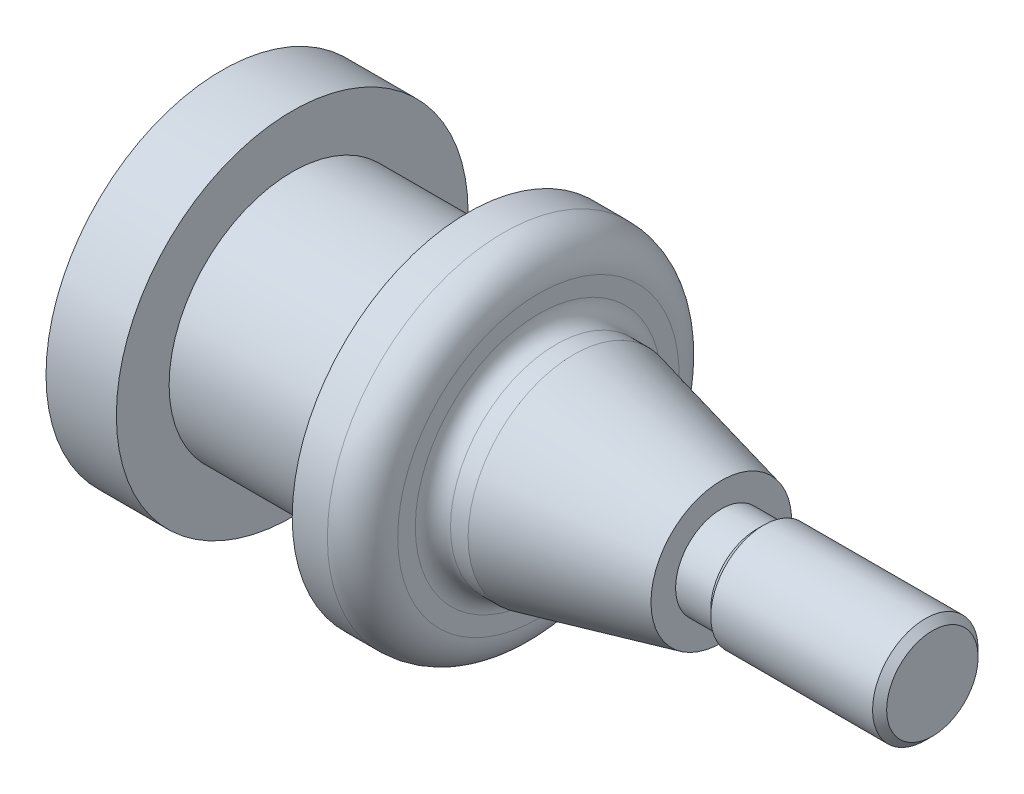
SolidWorks part; units mm, degrees
ref_plane "Front Plane" through (0, 0, 0) normal (0, 0, 1) x (1, 0, 0)
ref_plane "Top Plane" through (0, 0, 0) normal (0, 1, 0) x (1, 0, 0)
ref_plane "Right Plane" through (0, 0, 0) normal (1, 0, 0) x (0, 0, -1)
sketch "Sketch1" plane through (0, 0, 0) normal (0, 0, 1) x (1, 0, 0)
  line L0 (0, 0) -> (202, 0)
  line L1 (202, 0) -> (202, 15)
  line L2 (202, 15) -> (152, 15)
  line L3 (152, 15) -> (152, 13)
  line L4 (152, 13) -> (142, 13)
  line L5 (142, 13) -> (142, 20)
  line L6 (142, 20) -> (100, 30)
  line L7 (100, 30) -> (90, 30)
  line L8 (90, 30) -> (90, 50)
  line L9 (90, 50) -> (70, 50)
  line L10 (70, 50) -> (70, 35)
  line L11 (70, 35) -> (20, 35)
  line L12 (20, 35) -> (20, 50)
  line L13 (20, 50) -> (0, 50)
  line L14 (0, 50) -> (0, 0)
  point P2 (147.3354, 16.2415)
  dimension "D1" = 202
  dimension "D2" = 50
  dimension "D3" = 35
  dimension "D4" = 50
  dimension "D5" = 20
  dimension "D6" = 50
  dimension "D7" = 20
  dimension "D8" = 10
  dimension "D9" = 15
  dimension "D10" = 50
  dimension "D11" = 13
  dimension "D12" = 20
  dimension "D13" = 30
  dimension "D14" = 30
revolve "Revolve1" add sketch "Sketch1" angle 360 about L0
fillet "Fillet1" radius 5 1 edges at (90, 0, 30)
fillet "Fillet2" radius 10 1 edges at (90, 0, 50)
chamfer "Chamfer1" distance 2 angle 45 2 edges at (152, 0, 15) (202, 0, 15)
